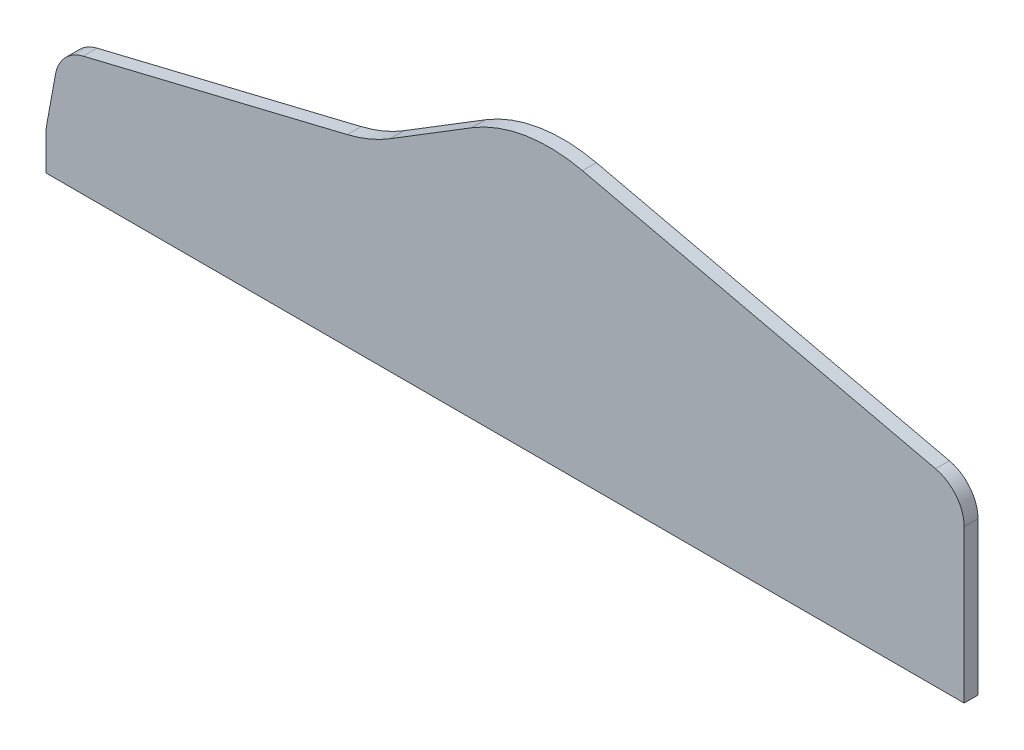
SolidWorks part; units mm, degrees
ref_plane "Front Plane" through (0, 0, 0) normal (0, 0, 1) x (1, 0, 0)
ref_plane "Top Plane" through (0, 0, 0) normal (0, 1, 0) x (1, 0, 0)
ref_plane "Right Plane" through (0, 0, 0) normal (1, 0, 0) x (0, 0, -1)
sketch "Sketch2" plane through (0, 0, 0) normal (0, 0, 1) x (1, 0, 0)
  line L0 (-318.7974, 52.106) -> (-105.4374, 103.886)
  line L1 (-105.4374, 103.886) -> (0, 168.8465)
  line L2 (0, 168.8465) -> (303.0919, 98.8)
  line L3 (303.0919, 98.8) -> (303.0919, 0)
  line L4 (303.0919, 0) -> (303.0919, -26.4)
  line L6 (303.0919, -26.4) -> (-328.3315, -26.4)
  line L7 (-328.3315, -26.4) -> (-328.3315, 0)
  spline S0 degree 1 poles (-328.3315, 0) (-318.7974, 52.106) knots 0 0 1 1
  dimension "D1" = 9.5341
  dimension "D2" = 52.106
  dimension "D3" = 213.36
  dimension "D4" = 51.78
  dimension "D5" = 105.4374
  dimension "D6" = 64.9605
  dimension "D7" = 303.0919
  dimension "D8" = 98.8
  dimension "D9" = 26.4
extrude "Boss-Extrude1" add sketch "Sketch2" along normal mid plane 9.525
fillet "Fillet1" radius 25.4 3 edges at (-318.7974, 52.106, 0) (303.0919, 98.8, 0) (-328.3315, 0, 0)
fillet "Fillet2" radius 101.6 2 edges at (0, 168.8465, 0) (-105.4374, 103.886, 0)
